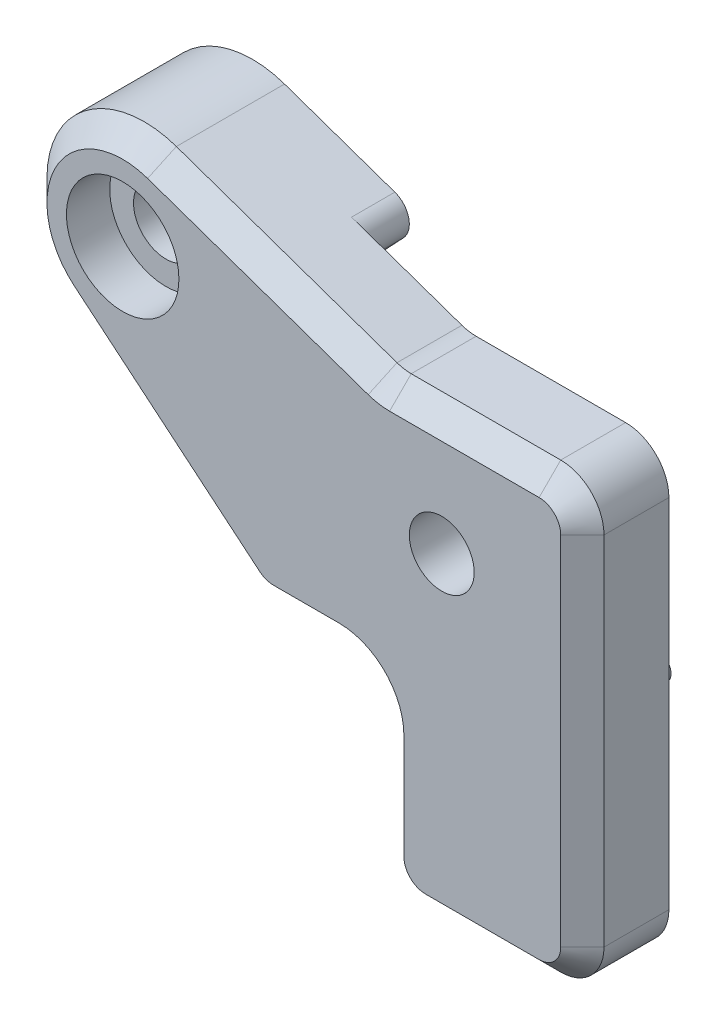
SolidWorks part; units mm, degrees
ref_plane "Front Plane" through (0, 0, 0) normal (0, 0, 1) x (1, 0, 0)
ref_plane "Top Plane" through (0, 0, 0) normal (0, 1, 0) x (1, 0, 0)
ref_plane "Right Plane" through (0, 0, 0) normal (1, 0, 0) x (0, 0, -1)
sketch "Sketch1" plane through (0, 0, 0) normal (0, 0, 1) x (1, 0, 0)
  line L0 (-2.75, -15) -> (-2.75, -6.15)
  line L1 (6.5, -15) -> (-2.75, -15)
  line L2 (6.5, -15) -> (6.5, 5.5)
  line L3 (6.5, 5.5) -> (-2.75, 5.5)
  line L7 (-13.2679, 9.1688) -> (-2.75, 5.5)
  line L8 (6.5, 5.5) -> (6.5, -15) construction
  line L9 (-2.75, 5.5) -> (6.5, 5.5) construction
  line L10 (-2.75, -6.15) -> (-2.75, -15) construction
  line L11 (6.5, -15) -> (-2.75, -15) construction
  line L12 (-2.75, -6.15) -> (-2.75, 5.5) construction
  line L13 (-17.6317, 1.4636) -> (-8.5, -6.15)
  line L14 (-8.5, -6.15) -> (-2.75, -6.15)
  line L15 (-2.75, -6.15) -> (-8.5, -6.15) construction
  line L16 (-16.25, 4.9199) -> (-19.25, 4.9199) construction
  circle A0 centre (0, 0) radius 1.25 construction
  circle A1 centre (0, 0) radius 1.5
  circle A2 centre (-14.75, 4.9199) radius 1.5
  arc A3 (-15.5, 3.6208) -> (-15.5, 6.2189) centre (-14.75, 4.9199) ccw construction
  arc A4 (-13.2679, 9.1688) -> (-17.6317, 1.4636) centre (-14.75, 4.9199) ccw
  dimension "D2" = 2.5
  dimension "D3" = 3
  dimension "D1" = 0.25
extrude "Boss-Extrude1" add sketch "Sketch1" against normal blind 2
fillet "Fillet1" radius 2 6 edges at (6.5, -15, -1) (-8.5, -6.15, -1) (-2.75, 5.5, -1) (6.5, 5.5, -1) (-2.75, -15, -1) (-2.75, -6.15, -1)
sketch "Sketch2" plane through (0, 0, 0) normal (0, 0, 1) x (1, 0, 0)
  line L7 (-0.75, -15) -> (4.5, -15)
  line L8 (6.5, -13) -> (6.5, 3.5)
  line L9 (4.5, 5.5) -> (-2.4112, 5.5)
  line L10 (-3.0699, 5.6116) -> (-13.2679, 9.1688)
  line L11 (-17.6317, 1.4636) -> (-9.0564, -5.6861)
  line L12 (-7.7756, -6.15) -> (-4.75, -6.15)
  line L13 (-2.75, -8.15) -> (-2.75, -13)
  line L14 (-0.75, -15) -> (4.5, -15)
  line L15 (6.5, -13) -> (6.5, 3.5)
  line L16 (4.5, 5.5) -> (-2.4112, 5.5)
  line L17 (-3.0699, 5.6116) -> (-13.2679, 9.1688)
  line L18 (-17.6317, 1.4636) -> (-9.0564, -5.6861)
  line L19 (-7.7756, -6.15) -> (-4.75, -6.15)
  line L20 (-2.75, -8.15) -> (-2.75, -13)
  circle A0 centre (0, 0) radius 1.5 construction
  circle A1 centre (0, 0) radius 1.5
  circle A2 centre (-14.75, 4.9199) radius 2.35 construction
  circle A3 centre (-14.75, 4.9199) radius 1.5 construction
  circle A4 centre (-14.75, 4.9199) radius 2.6
  arc A7 (4.5, -15) -> (6.5, -13) centre (4.5, -13) ccw
  arc A8 (6.5, 3.5) -> (4.5, 5.5) centre (4.5, 3.5) ccw
  arc A9 (-3.0699, 5.6116) -> (-2.4112, 5.5) centre (-2.4112, 7.5) ccw
  arc A10 (-13.2679, 9.1688) -> (-17.6317, 1.4636) centre (-14.75, 4.9199) ccw
  arc A11 (-9.0564, -5.6861) -> (-7.7756, -6.15) centre (-7.7756, -4.15) ccw
  arc A12 (-2.75, -8.15) -> (-4.75, -6.15) centre (-4.75, -8.15) ccw
  arc A13 (-2.75, -13) -> (-0.75, -15) centre (-0.75, -13) ccw
  arc A14 (4.5, -15) -> (6.5, -13) centre (4.5, -13) ccw
  arc A15 (6.5, 3.5) -> (4.5, 5.5) centre (4.5, 3.5) ccw
  arc A16 (-3.0699, 5.6116) -> (-2.4112, 5.5) centre (-2.4112, 7.5) ccw
  arc A17 (-13.2679, 9.1688) -> (-17.6317, 1.4636) centre (-14.75, 4.9199) ccw
  arc A18 (-9.0564, -5.6861) -> (-7.7756, -6.15) centre (-7.7756, -4.15) ccw
  arc A19 (-2.75, -8.15) -> (-4.75, -6.15) centre (-4.75, -8.15) ccw
  arc A20 (-2.75, -13) -> (-0.75, -15) centre (-0.75, -13) ccw
  dimension "D3" = 4.7
extrude "Boss-Extrude2" add sketch "Sketch2" along normal blind 2
chamfer "Chamfer1" distance 1 angle 45 14 edges at (1.875, -15, 2) (5.9142, -14.4142, 2) (-2.1642, -14.4142, 2) (6.5, -4.75, 2) (-2.75, -10.575, 2) (5.9142, 4.9142, 2) (-3.3358, -6.7358, 2) (1.0444, 5.5, 2) (-6.2628, -6.15, 2) (-2.7452, 5.5281, 2) (-8.4567, -6.0305, 2) (-8.1689, 7.3902, 2) (-13.344, -2.1113, 2) (-18.6656, 7.1375, 2)
sketch "Sketch3" plane through (0, 0, -2) normal (0, 0, -1) x (-1, 0, 0)
  line L0 (0, 0) -> (0, -9.5) construction
  circle A0 centre (0, -9.5) radius 1.25 construction
  circle A1 centre (0, -9.5) radius 1
  dimension "D3" = 2.5
  dimension "D1" = 9.5
extrude "Boss-Extrude3" add sketch "Sketch3" along normal blind 6
chamfer "Chamfer2" distance 3.5 distance2 0.4 1 edges at (-1, -9.5, -8) first distance on face at (-1, -9.5, -8)
sketch "Sketch4" plane through (0, 0, -2) normal (0, 0, -1) x (-1, 0, 0)
  line L0 (13.2679, 9.1688) -> (8.1689, 7.3902)
  line L1 (7.7709, 5.7597) -> (11.4769, 1.8317)
  line L2 (3.0699, 5.6116) -> (13.2679, 9.1688) construction
  circle A0 centre (14.75, 4.9199) radius 1.5 construction
  circle A1 centre (14.75, 4.9199) radius 1.5
  arc A4 (11.4769, 1.8317) -> (13.2679, 9.1688) centre (14.75, 4.9199) ccw
  arc A5 (17.6317, 1.4636) -> (13.2679, 9.1688) centre (14.75, 4.9199) ccw construction
  arc A6 (8.1689, 7.3902) -> (7.7709, 5.7597) centre (8.4983, 6.446) ccw
  dimension "D1" = 1
extrude "Boss-Extrude4" add sketch "Sketch4" along normal offset from surface (2 mm away) 6 up to face at (-3.0922, -3.4294, 2)
equation "\"Tolerance\" = 0.25mm"
equation "\"Pocket_Head_M5\"= 8mm"
equation "\"Pocket_Head_M4\" = 7mm"
equation "\"Pocket_Nut_M4\" = 7mm"
equation "\"Pocket_Nut_M5\"= 8mm"
equation "\"Pocket_Nut_M3\"= 5.5mm"
equation "\"Pocket_Head_M3\"= 5.5mm"
equation "\"D1@Sketch1\"=\"Tolerance\""
equation "\"D2@Sketch2\"=\"Tolerance\""
equation "\"Pocket_Head_M2.5\" = 4.7mm"
equation "\"D3@Sketch2\"=\"Pocket_Head_M2.5\""
equation "\"D2@Sketch3\"=\"Tolerance\""
